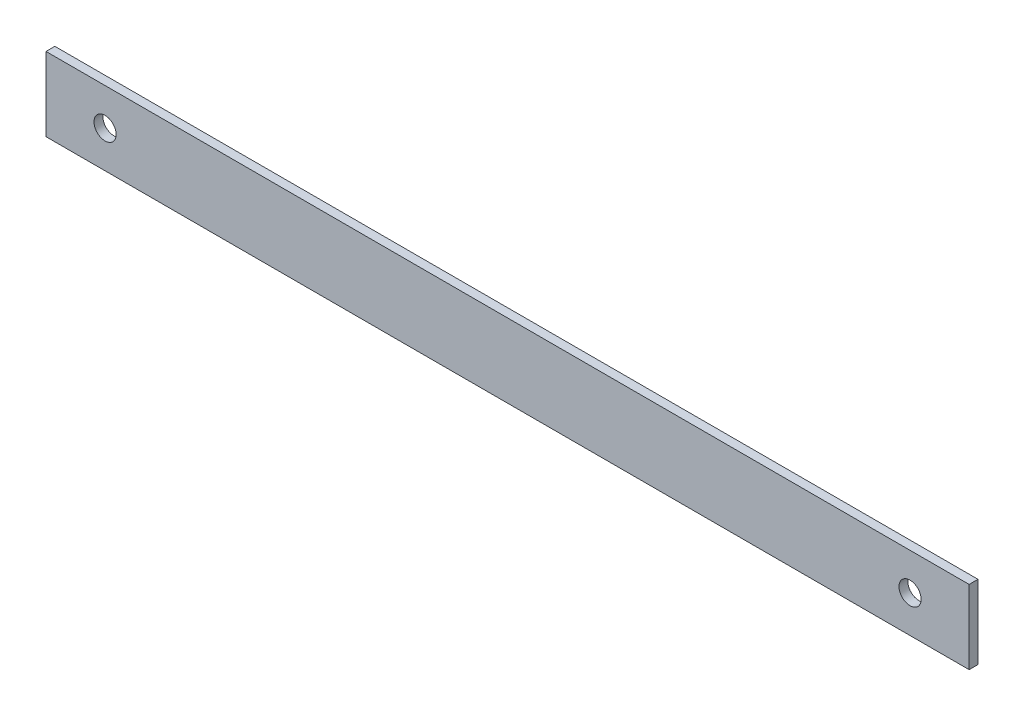
SolidWorks part; units mm, degrees
material "Brass"
ref_plane "Front Plane" through (0, 0, 0) normal (0, 0, 1) x (1, 0, 0)
ref_plane "Top Plane" through (0, 0, 0) normal (0, 1, 0) x (1, 0, 0)
ref_plane "Right Plane" through (0, 0, 0) normal (1, 0, 0) x (0, 0, -1)
sketch "Sketch1" plane through (0, 0, 0) normal (0, 0, 1) x (1, 0, 0)
  line L0 (0, 0) -> (125, 0)
  line L1 (125, 0) -> (125, 10)
  line L2 (125, 10) -> (0, 10)
  line L3 (0, 10) -> (0, 0)
  dimension "D1" = 125
  dimension "D2" = 10
extrude "Boss-Extrude1" add sketch "Sketch1" along normal blind 1.2
sketch "Sketch2" plane through (0, 0, 0) normal (0, 0, 1) x (1, 0, 0)
  circle A0 centre (8, 5) radius 1.5
  circle A1 centre (117, 5) radius 1.5
  dimension "D3" = 3
  dimension "D6" = 3
  dimension "D1" = 8
  dimension "D2" = 5
  dimension "D4" = 117
  dimension "D5" = 5
extrude "Cut-Extrude1" cut sketch "Sketch2" against normal mid plane 10
